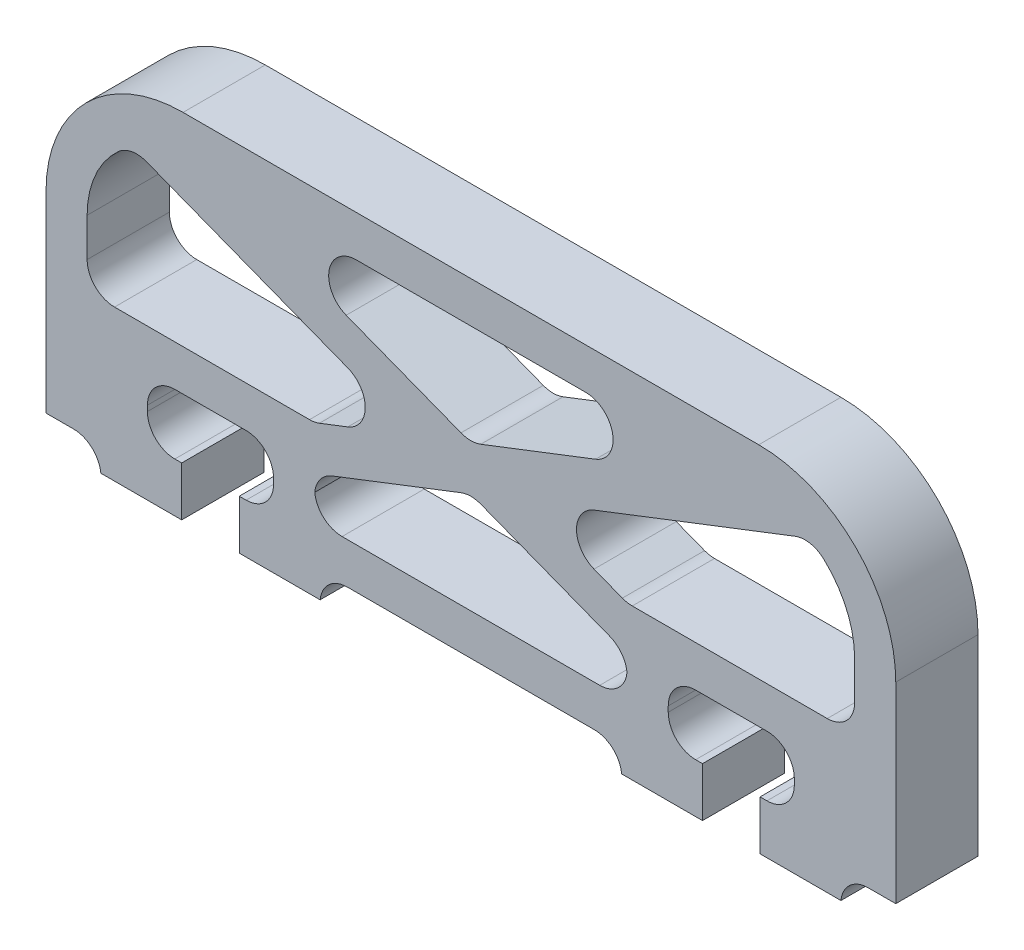
SolidWorks part; units mm, degrees
ref_plane "Front Plane" through (0, 0, 0) normal (0, 0, 1) x (1, 0, 0)
ref_plane "Top Plane" through (0, 0, 0) normal (0, 1, 0) x (1, 0, 0)
ref_plane "Right Plane" through (0, 0, 0) normal (1, 0, 0) x (0, 0, -1)
sketch "Sketch1" plane through (0, 0, 0) normal (0, 0, 1) x (1, 0, 0)
  line L0 (-9.5, -6.9) -> (-9.5, 6) construction
  line L1 (-15.5, 6) -> (15.5, 6)
  line L2 (-15.5, 6) -> (-15.5, -6)
  line L3 (-15.5, -6) -> (15.5, -6)
  line L4 (15.5, 6) -> (15.5, -6)
  line L5 (-15.5, 6) -> (15.5, -6) construction
  line L6 (-15.5, -6) -> (15.5, 6) construction
  line L7 (-15.5, -6) -> (-5.5, -6)
  line L9 (-13.5, -6.9) -> (-5.5, -6.9)
  line L10 (-5.5, -6) -> (-5.5, -6.9)
  line L11 (0, 6) -> (0, -6) construction
  line L12 (-10.55, -5.1) -> (-8.45, -5.1)
  line L13 (-10.55, -5.1) -> (-10.55, -6.9)
  line L14 (-10.55, -6.9) -> (-8.45, -6.9)
  line L15 (-8.45, -5.1) -> (-8.45, -6.9)
  line L16 (-10.55, -5.1) -> (-8.45, -6.9) construction
  line L17 (-10.55, -6.9) -> (-8.45, -5.1) construction
  line L18 (-11.8, -2.9) -> (-7.2, -2.9)
  line L19 (-11.8, -2.9) -> (-11.8, -5.1)
  line L20 (-11.8, -5.1) -> (-7.2, -5.1)
  line L21 (-7.2, -2.9) -> (-7.2, -5.1)
  line L22 (-11.8, -2.9) -> (-7.2, -5.1) construction
  line L23 (-11.8, -5.1) -> (-7.2, -2.9) construction
  line L24 (11.8, -2.9) -> (7.2, -2.9)
  line L25 (11.8, -2.9) -> (11.8, -5.1)
  line L26 (11.8, -5.1) -> (7.2, -5.1)
  line L27 (7.2, -2.9) -> (7.2, -5.1)
  line L28 (10.55, -5.1) -> (8.45, -5.1)
  line L29 (10.55, -5.1) -> (10.55, -6.9)
  line L30 (10.55, -6.9) -> (8.45, -6.9)
  line L31 (8.45, -5.1) -> (8.45, -6.9)
  line L32 (15.5, -6) -> (5.5, -6)
  line L33 (5.5, -6) -> (5.5, -6.9)
  line L34 (13.5, -6.9) -> (5.5, -6.9)
  line L36 (-13.5, -6.9) -> (-13.5, -6)
  line L37 (13.5, -6.9) -> (13.5, -6)
  point P0 (0, 0)
  point P11 (-9.5, -6)
  point P16 (-9.5, -4)
  dimension "D1" = 31
  dimension "D2" = 12
  dimension "D3" = 0.9
  dimension "D4" = 8
  dimension "D5" = 2.1
  dimension "D6" = 0.9
  dimension "D7" = 2.2
  dimension "D8" = 4.6
  dimension "D9" = 2
extrude "Base shape" add sketch "Sketch1" along normal blind 3 contours L31 L26 L27 L24 L25 L29 L3 L4 L1 L2 L13 L20 L19 L18 L21 L15 | L3 L15 L9 L10 | L13 L3 L9 | L34 L31 L3 L33 | L3 L29 L34 region at (0, 0.2929, 0) region at (-12.025, -6.45, 0) region at (12.025, -6.45, 0) region at (-6.975, -6.45, 0) region at (6.975, -6.45, 0)
fillet "Edge radiuses" radius 5 2 edges at (15.5, 6, 1.5) (-15.5, 6, 1.5)
sketch "Sketch2" plane through (0, 0, 3) normal (0, 0, 1) x (1, 0, 0)
  line L0 (-5.5, -6) -> (5.5, -6) construction
  line L1 (15.5, -6) -> (-15.5, -6)
  line L2 (15.5, -6) -> (15.5, 6)
  line L3 (15.5, 6) -> (-15.5, 6)
  line L4 (-15.5, -6) -> (-15.5, 6)
  line L5 (15.5, -6) -> (-15.5, 6) construction
  line L6 (15.5, 6) -> (-15.5, -6) construction
  line L8 (15.7715, -5.2986) -> (-15.2285, 6.7014)
  line L9 (15.2285, 6.7014) -> (-15.7715, -5.2986)
  line L10 (15.2285, -6.7014) -> (-15.7715, 5.2986)
  line L11 (15.7715, 5.2986) -> (-15.2285, -6.7014)
  line L36 (-15.5, 1) -> (-15.5, -6) construction
  line L37 (-13.3, -1.4) -> (-14, -1.4)
  line L38 (13.3, -1.4) -> (14, -1.4)
  line L60 (10.5, 4.5) -> (-10.5, 4.5)
  line L61 (14, -4.5) -> (14, 1)
  line L62 (-13.3, -1.4) -> (-5.7, -1.4)
  line L63 (-5.7, -1.4) -> (-5.7, -4.5)
  line L64 (-5.7, -4.5) -> (5.7, -4.5)
  line L65 (5.7, -4.5) -> (5.7, -1.4)
  line L66 (5.7, -1.4) -> (13.3, -1.4)
  line L67 (14, -4.5) -> (14, 1)
  line L68 (10.5, 4.5) -> (-10.5, 4.5)
  line L70 (-13.3, -1.4) -> (-5.7, -1.4)
  line L71 (-5.7, -1.4) -> (-5.7, -4.5)
  line L72 (-5.7, -4.5) -> (5.7, -4.5)
  line L73 (5.7, -4.5) -> (5.7, -1.4)
  line L74 (5.7, -1.4) -> (13.3, -1.4)
  line L80 (-14, 1) -> (-14, -4.5)
  line L81 (-14, 1) -> (-14, -4.5)
  line L83 (-13.3, -4.5) -> (-13.3, -1.4)
  line L84 (-13.3, -4.5) -> (-13.3, -1.4)
  line L85 (13.3, -1.4) -> (13.3, -4.5)
  line L86 (13.3, -1.4) -> (13.3, -4.5)
  line L87 (13.3, -4.5) -> (14, -4.5)
  line L88 (13.3, -4.5) -> (14, -4.5)
  line L89 (-14, -4.5) -> (-13.3, -4.5)
  line L90 (-14, -4.5) -> (-13.3, -4.5)
  arc A4 (14, 1) -> (10.5, 4.5) centre (10.5, 1) ccw
  arc A5 (14, 1) -> (10.5, 4.5) centre (10.5, 1) ccw
  arc A8 (-10.5, 4.5) -> (-14, 1) centre (-10.5, 1) ccw
  arc A9 (-10.5, 4.5) -> (-14, 1) centre (-10.5, 1) ccw
  point P0 (0, 0)
  dimension "D3" = 1.5
extrude "Inner cuts" cut sketch "Sketch2" against normal up to next contours L10 A9 L81 L90 L9 L84 L70 | L9 L68 L8 | L67 A5 L11 L8 L74 L86 L88 | L72 L73 L10 L11 L71 region at (0, -3.1265, 3) region at (9.4493, 0.6558, 3) region at (-9.4493, 0.6558, 3) region at (0, 3.2688, 3)
fillet "1mm milling radiuses" radius 1 28 edges at (5.7, -4.5, 1.5) (5.7, -3.0129, 1.5) (-5.7, -4.5, 1.5) (-5.7, -3.0129, 1.5) (0, -0.8065, 1.5) (5.7, -1.4, 1.5) (2.0833, 0, 1.5) (9.5417, 4.5, 1.5) (-9.5417, 4.5, 1.5) (0, 0.8065, 1.5) (-2.0833, 0, 1.5) (-5.7, -1.4, 1.5) (14, -1.4, 1.5) (12.3469, 3.973, 1.5) (-12.3469, 3.973, 1.5) (-14, -1.4, 1.5) (-7.2, -2.9, 1.5) (-7.2, -5.1, 1.5) (11.8, -5.1, 1.5) (11.8, -2.9, 1.5) (7.2, -2.9, 1.5) (7.2, -5.1, 1.5) (-11.8, -5.1, 1.5) (-11.8, -2.9, 1.5) (13.5, -6, 1.5) (5.5, -6, 1.5) (-13.5, -6, 1.5) (-5.5, -6, 1.5)
